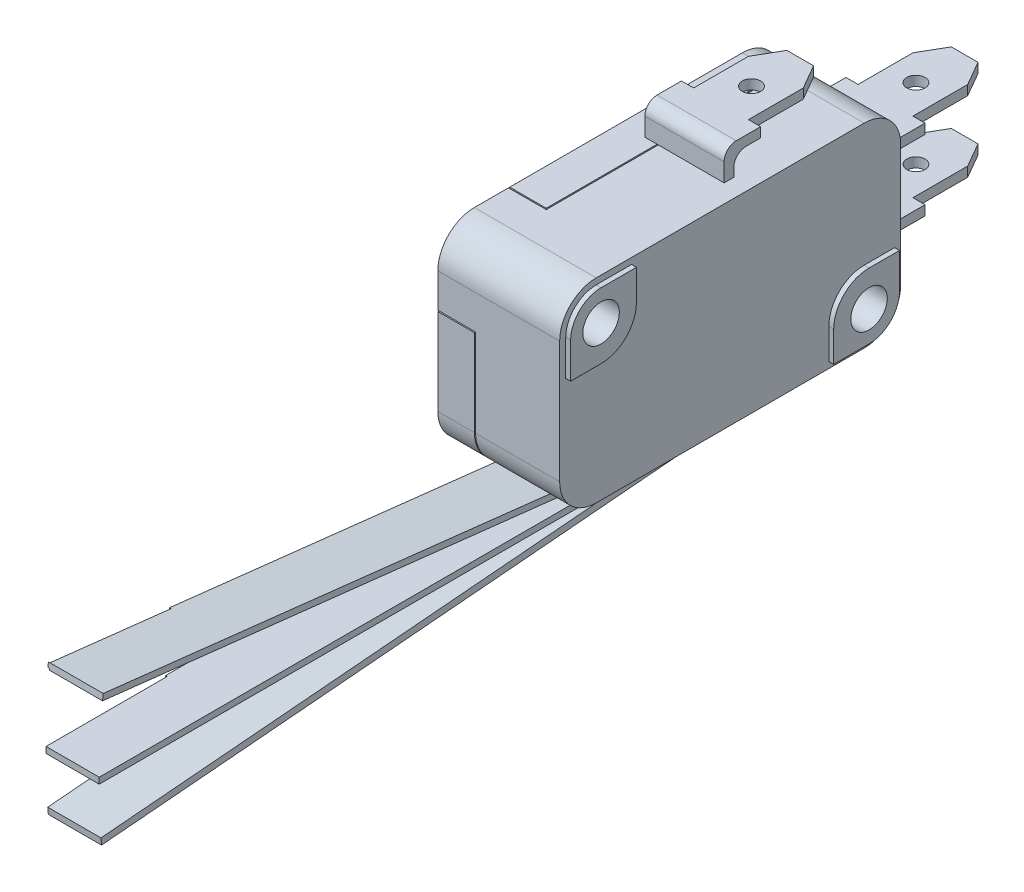
SolidWorks part; units mm, degrees
ref_plane "前视基准面" through (0, 0, 0) normal (0, 0, 1) x (1, 0, 0)
ref_plane "上视基准面" through (0, 0, 0) normal (0, 1, 0) x (1, 0, 0)
ref_plane "右视基准面" through (0, 0, 0) normal (1, 0, 0) x (0, 0, -1)
sketch "草图1" plane through (0, 0, 0) normal (1, 0, 0) x (0, 0, -1)
  line L1 (14, -8) -> (-14, -8)
  line L2 (14, -8) -> (14, 8)
  line L3 (14, 8) -> (-14, 8)
  line L4 (-14, -8) -> (-14, 8)
  line L5 (14, -8) -> (-14, 8) construction
  line L6 (14, 8) -> (-14, -8) construction
  circle A0 centre (11, -5) radius 1.5
  circle A1 centre (-11, 5) radius 1.5
  point P0 (0, 0)
  dimension "D3" = 3
  dimension "D1" = 28
  dimension "D2" = 16
  dimension "D4" = 3
  dimension "D5" = 3
  dimension "D6" = 3
  dimension "D7" = 3
extrude "凸台-拉伸1" add sketch "草图1" along normal blind 10
fillet "圆角1" radius 3 4 edges at (5, 8, -14) (5, 8, 14) (5, -8, 14) (5, -8, -14)
sketch "草图2" plane through (10, 0, 0) normal (1, 0, 0) x (0, 0, -1)
  line L0 (13.5, -5) -> (13.5, -2.1)
  line L2 (13.5, -2.1) -> (11, -2.1)
  line L3 (8.1, -5) -> (8.1, -7.5)
  line L5 (11, -7.5) -> (8.1, -7.5)
  line L6 (-11, 2.1) -> (-13.5, 2.1)
  line L8 (-8.1, 5) -> (-8.1, 7.5)
  line L10 (-11, 7.5) -> (-8.1, 7.5)
  line L11 (-13.5, 5) -> (-13.5, 2.1)
  arc A1 (11, -7.5) -> (13.5, -5) centre (11, -5) ccw
  circle A2 centre (11, -5) radius 1.5 construction
  circle A3 centre (11, -5) radius 1.5
  circle A5 centre (-11, 5) radius 1.5 construction
  arc A6 (-11, 2.1) -> (-8.1, 5) centre (-11, 5) ccw
  circle A7 centre (-11, 5) radius 1.5
  arc A8 (11, -2.1) -> (8.1, -5) centre (11, -5) ccw
  arc A9 (11, -8) -> (14, -5) centre (11, -5) ccw construction
  arc A10 (-11, 7.5) -> (-13.5, 5) centre (-11, 5) ccw
  dimension "D1" = 5.8
  dimension "D2" = 0.5
extrude "凸台-拉伸2" add sketch "草图2" along normal blind 0.4
sketch "草图3" plane through (0, 0, 0) normal (-1, 0, 0) x (0, 0, 1)
  line L0 (-13.5, -2.1) -> (-11, -2.1) construction
  line L1 (-8.1, -5) -> (-8.1, -7.5) construction
  line L2 (13.5, 2.1) -> (11, 2.1) construction
  line L3 (8.1, 5) -> (8.1, 7.5) construction
  line L4 (-13.5, -2.1) -> (-11, -2.1)
  line L5 (-8.1, -5) -> (-8.1, -7.5)
  line L6 (13.5, 2.1) -> (11, 2.1)
  line L7 (8.1, 5) -> (8.1, 7.5)
  line L8 (13.5, 2.1) -> (14, 2.1)
  line L9 (14, 5) -> (14, -5) construction
  line L10 (8.1, 7.5) -> (8.1, 8)
  line L11 (-11, 8) -> (11, 8) construction
  line L12 (13.5, 2.2) -> (14, 2.2)
  line L13 (13.5, 2.2) -> (11, 2.2)
  line L14 (8.2, 5) -> (8.2, 7.5)
  line L15 (8.2, 7.5) -> (8.2, 8)
  line L16 (8.2, 8) -> (8.1, 8)
  line L17 (14, 2.1) -> (14, 2.2)
  line L18 (-8.1, -7.5) -> (-8.1, -8)
  line L19 (11, -8) -> (-11, -8) construction
  line L20 (-13.5, -2.1) -> (-14, -2.1)
  line L21 (-14, -5) -> (-14, 5) construction
  line L22 (-13.5, -2.2) -> (-14, -2.2)
  line L23 (-13.5, -2.2) -> (-11, -2.2)
  line L24 (-8.2, -5) -> (-8.2, -7.5)
  line L25 (-8.2, -7.5) -> (-8.2, -8)
  line L26 (-14, -2.1) -> (-14, -2.2)
  line L27 (-8.1, -8) -> (-8.2, -8)
  arc A0 (-8.1, -5) -> (-11, -2.1) centre (-11, -5) ccw construction
  arc A1 (8.1, 5) -> (11, 2.1) centre (11, 5) ccw construction
  arc A2 (-8.1, -5) -> (-11, -2.1) centre (-11, -5) ccw
  arc A3 (8.1, 5) -> (11, 2.1) centre (11, 5) ccw
  arc A4 (8.2, 5) -> (11, 2.2) centre (11, 5) ccw
  arc A5 (-8.2, -5) -> (-11, -2.2) centre (-11, -5) ccw
  dimension "D1" = 0.1
  dimension "D2" = 0.1
extrude "切除-拉伸1" cut sketch "草图3" against normal blind 0.1
sketch "草图4" plane through (0, 8, 0) normal (0, 1, 0) x (1, 0, 0)
  line L0 (0, -8.2) -> (3.1, -8.2)
  line L1 (3.1, -8.2) -> (3.1, 14)
  line L2 (0, 14) -> (10, 14) construction
  line L3 (0, -8.1) -> (3, -8.1)
  line L4 (3, -8.1) -> (3, 14)
  line L5 (3, 14) -> (3.1, 14)
  line L6 (0, -8.2) -> (0, -8.1)
  line L7 (0, 11) -> (0, -8.1) construction
  dimension "D1" = 3
extrude "切除-拉伸2" cut sketch "草图4" against normal blind 3
sketch "草图5" plane through (0, 0, -14) normal (0, 0, -1) x (-1, 0, 0)
  line L0 (-3, 5) -> (-3, -2.1)
  line L1 (-3, -2.1) -> (-0.1, -2.1)
  line L2 (-0.1, -2.1) -> (-0.1, -2.2)
  line L3 (-0.1, -2.2) -> (-3.1, -2.2)
  line L4 (-3.1, -2.2) -> (-3.1, 5)
  line L5 (-3.1, 5) -> (-3, 5)
extrude "切除-拉伸3" cut sketch "草图5" against normal blind 0.1
sketch "草图6" plane through (3.1, 0, 0) normal (-1, 0, 0) x (0, 0, 1)
  line L0 (-8.2, -8) -> (11, -8)
  line L2 (14, 2.1) -> (14, -5) construction
  line L3 (14, 2.1) -> (14, -5)
  line L4 (14, 2.1) -> (14, 2.2)
  line L5 (-8.2, -7.9) -> (11, -7.9)
  line L7 (13.9, 2.1) -> (13.9, -5)
  line L8 (13.9, 2.1) -> (13.9, 2.2)
  line L9 (13.9, 2.2) -> (14, 2.2)
  line L10 (-8.2, -7.9) -> (-8.2, -8)
  arc A0 (11, -8) -> (14, -5) centre (11, -5) ccw construction
  arc A1 (11, -8) -> (14, -5) centre (11, -5) ccw
  arc A2 (11, -7.9) -> (13.9, -5) centre (11, -5) ccw
  dimension "D1" = 0.1
extrude "切除-拉伸4" cut sketch "草图6" along normal blind 0.1
sketch "草图7" plane through (0, 0, 14) normal (0, 0, 1) x (1, 0, 0)
  line L0 (0.1, 2.2) -> (3, 2.2)
  line L1 (3, 2.2) -> (3, 2.1)
  line L2 (3, 2.2) -> (3, -5) construction
  line L3 (3, 2.1) -> (0.1, 2.1)
  line L4 (0.1, 2.1) -> (0.1, 2.2)
extrude "切除-拉伸5" cut sketch "草图7" against normal blind 0.1
sketch "草图8" plane through (0, -8, 0) normal (0, -1, 0) x (1, 0, 0)
  line L0 (0.1, -8.2) -> (0.1, -8.1)
  line L1 (0.1, -8.1) -> (3, -8.1)
  line L2 (3, -8.2) -> (3, 11) construction
  line L3 (3, -8.1) -> (3, -8.2)
  line L4 (3, -8.2) -> (0.1, -8.2)
extrude "切除-拉伸6" cut sketch "草图8" against normal blind 0.1
sketch "草图10" plane through (3.1, 0, 0) normal (-1, 0, 0) x (0, 0, 1)
  line L0 (-2.6, -8) -> (-2.6, -10)
  line L1 (11, -8) -> (-8.1, -8) construction
  line L2 (-2.6, -10) -> (49.4, -10)
  line L3 (-2.1, -8) -> (-2.1, -9.5)
  line L4 (-2.1, -9.5) -> (49.4, -9.5)
  line L5 (-14, -5) -> (-14, -2.2) construction
  line L6 (49.4, -10) -> (49.4, -9.5)
  line L7 (11, -8.08) -> (11, -8)
  line L8 (11, -8) -> (8.2, -8)
  line L9 (8.2, -8) -> (8.2, -8.08)
  line L10 (14, 2.1) -> (14, -5) construction
  line L11 (-2.6, -8) -> (-2.1, -8)
  line L12 (9.6, -8) -> (9.6, -10.5) construction
  line L13 (-2.1, -9.5) -> (9.6, -10.5) construction
  line L14 (-2.6, -10) -> (9.6, -11.0427) construction
  line L15 (14.7373, -9.5714) -> (45.4566, 5) construction
  line L16 (11, 5) -> (45.4566, 5) construction
  line L17 (14.9691, -10.0601) -> (45.6884, 4.5113) construction
  line L18 (45.4566, 5) -> (45.6884, 4.5113) construction
  line L19 (3.75, -10) -> (9.6, -10.5)
  line L20 (-2.6, -10) -> (9.6, -11.0427) construction
  line L21 (14.9691, -10.0601) -> (15.0958, -10)
  line L22 (-2.1, -9.5) -> (8.2231, -8.333)
  line L23 (2.3512, -9.5) -> (8.4086, -8.8152)
  line L24 (49.1302, -4.2119) -> (49.0741, -3.715)
  line L25 (10.8812, -8.5357) -> (49.1302, -4.2119)
  line L26 (11, -8.0191) -> (49.0741, -3.715)
  line L27 (11.7771, -7.9313) -> (11.7771, -7.9813)
  line L28 (11.7771, -7.9813) -> (11, -8.0691)
  line L29 (-2.6, -10) -> (49.2111, -14.4283)
  line L30 (9.6, -10.5) -> (49.2572, -13.8895)
  line L31 (49.2111, -14.4283) -> (49.2572, -13.8895)
  arc A0 (8.2, -8.08) -> (11, -8.08) centre (9.6, -8.08) ccw
  circle A1 centre (9.6, -9.1) radius 1.4 construction
  arc A2 (9.6, -10.5) -> (14.7373, -9.5714) centre (10.4516, -0.5363) ccw construction
  circle A3 centre (11, 5) radius 1.5 construction
  arc A4 (9.6, -11.0427) -> (14.9691, -10.0601) centre (10.4516, -0.5363) ccw construction
  arc A5 (9.6, -10.5) -> (13.6825, -10) centre (10.4516, -0.5363) ccw construction
  arc A6 (11, -8) -> (14, -5) centre (11, -5) ccw construction
  line M10 (-8.2, -8) -> (11, -8)
  dimension "D6" = 3
  dimension "D8" = 1.42
  dimension "D9" = 2.5
  dimension "D10" = 10
  dimension "D12" = 0.05
  dimension "D1" = 0.5
  dimension "D2" = 11.4
  dimension "D3" = 2
  dimension "D4" = 52
  dimension "D5" = 90
  dimension "D7" = 2.8
  dimension "D11" = 34
extrude "凸台-拉伸3" add sketch "草图10" against normal blind 4.5 contours L2 L6 L4 L3 L0 M10 | L9 A0 L7 M10 region at (3.1, -9.722, 22.678) region at (3.1, -8.6312, 9.6)
ref_plane "基准面1" through (2, 0, 0) normal (-1, 0, 0) x (0, 0, 1)
sketch "草图11" plane through (2, 0, 0) normal (-1, 0, 0) x (0, 0, 1)
  line L0 (-14, 4) -> (-24, 4)
  line L1 (-14, -2.1) -> (-14, 5) construction
  line L2 (-24, 4) -> (-24, 3.2)
  line L3 (-24, 3.2) -> (-14, 3.2)
  line L4 (-14, 3.2) -> (-14, 4)
  line L5 (-11, 8) -> (8.1, 8) construction
  line L6 (-14, -1.8) -> (-24, -1.8)
  line L7 (-24, -1.8) -> (-24, -2.6)
  line L8 (-24, -2.6) -> (-14, -2.6)
  line L9 (-14, -2.6) -> (-14, -1.8)
  line L10 (-1, 8) -> (-1, 10.5)
  line L11 (-1, 10.5) -> (-10.5, 10.5)
  line L12 (-10.5, 10.5) -> (-10.5, 9.7)
  line L13 (-10.5, 9.7) -> (-1.8, 9.7)
  line L14 (-1.8, 9.7) -> (-1.8, 8)
  line L15 (-1.8, 8) -> (-1, 8)
  dimension "D1" = 10
  dimension "D2" = 0.8
  dimension "D3" = 4
  dimension "D4" = 5
  dimension "D5" = 2.5
  dimension "D6" = 13
  dimension "D7" = 9.5
extrude "凸台-拉伸4" add sketch "草图11" against normal blind 6.5
sketch "草图12" plane through (0, 4, 0) normal (0, 1, 0) x (1, 0, 0)
  line L0 (2, 17.5) -> (3, 17.5)
  line L1 (2, 8.8) -> (2, -8.8) construction
  line L2 (3, 17.5) -> (3, 22)
  line L3 (8.5, 24) -> (2, 24) construction
  line L4 (3, 24) -> (2, 24)
  line L5 (2, 24) -> (2, 17.5)
  line L6 (5.25, 24) -> (5.25, 20) construction
  line L7 (8.5, 24) -> (8.5, 17.5)
  line L8 (7.5, 24) -> (8.5, 24)
  line L9 (7.5, 17.5) -> (7.5, 22)
  line L10 (8.5, 17.5) -> (7.5, 17.5)
  line L11 (0, 14) -> (3, 14) construction
  line L12 (3, 22) -> (4.1547, 24)
  line L13 (4.1547, 24) -> (3, 24)
  line L14 (6.3453, 24) -> (7.5, 24)
  line L15 (7.5, 22) -> (6.3453, 24)
  circle A0 centre (5.25, 20) radius 0.75
  dimension "D3" = 1.5
  dimension "D4" = 4
  dimension "D1" = 4.5
  dimension "D2" = 3.5
  dimension "D5" = 30
  dimension "D6" = 2
extrude "切除-拉伸7" cut sketch "草图12" against normal through all
fillet "圆角2" radius 1 4 edges at (5.35, -9.5, -2.1) (5.35, -10, -2.6) (5.25, 9.7, -1.8) (5.25, 10.5, -1)
sketch "草图13" plane through (0, 10.5, 0) normal (0, 1, 0) x (1, 0, 0)
  line L0 (8.5, 10.5) -> (6.3453, 10.5)
  line L1 (8.5, 10.5) -> (2, 10.5) construction
  line L3 (8.5, 2) -> (8.5, 10.5) construction
  line L4 (8.5, 4) -> (8.5, 10.5)
  line L5 (6.3453, 10.5) -> (7.5, 8.5)
  line L7 (7.5, 8.5) -> (7.5, 4)
  line L8 (7.5, 4) -> (8.5, 4)
  line L9 (5.25, 10.5) -> (5.25, 3.2096) construction
  line L10 (6.3453, 24) -> (7.5, 22) construction
  line L11 (3, 4) -> (2, 4)
  line L12 (3, 8.5) -> (3, 4)
  line L13 (4.1547, 10.5) -> (3, 8.5)
  line L14 (2, 4) -> (2, 10.5)
  line L15 (2, 10.5) -> (4.1547, 10.5)
  circle A0 centre (5.25, 6.5) radius 0.75
  circle A1 centre (5.25, 20) radius 0.75 construction
  dimension "D4" = 4
  dimension "D1" = 6.5
  dimension "D2" = 60
  dimension "D3" = 4.5
extrude "切除-拉伸8" cut sketch "草图13" against normal blind 2
extrude "凸台-拉伸6" add sketch "草图10<5>" along direction (-1, 0, 0) on the side against the normal up to surface (4.5 mm away) contours A0 L22 L4 L23 | A0 L25 L24 L26 L27 L28 L7 region at (3.1, -9.0275, 4.1116) region at (3.1, -6.1146, 30.0782) up to face at (7.6, -9.1143, 10.7857)
sketch "草图10<5>" plane through (3.1, 0, 0) normal (-1, 0, 0) x (0, 0, 1) same geometry as "草图10"
extrude "凸台-拉伸7" add sketch "草图10<6>" along direction (-1, 0, 0) on the side against the normal up to surface (4.5 mm away) contours L29 L31 L30 L19 L2 region at (3.1, -12.0824, 24.87) up to face at (7.6, -8.2349, 13.8066)
sketch "草图10<6>" plane through (3.1, 0, 0) normal (-1, 0, 0) x (0, 0, 1) same geometry as "草图10"
sketch "草图14" plane through (3.1, 0, 0) normal (-1, 0, 0) x (0, 0, 1)
  line L1 (39.1351, -4.8386) -> (49.0722, -3.7152)
  line L2 (11.7771, -7.9313) -> (49.0741, -3.715) construction
  line L3 (39.3003, -13.5812) -> (49.2639, -14.4328)
  line L4 (-2.6, -10) -> (49.2111, -14.4283) construction
  arc A0 (39.3003, -13.5812) -> (39.1351, -4.8386) centre (-2.6, -10) ccw
  arc A1 (49.2639, -14.4328) -> (49.0722, -3.7152) centre (-2.6, -10) ccw
  dimension "D1" = 10
extrude "切除-拉伸9" cut sketch "草图14" against normal blind 0.13
